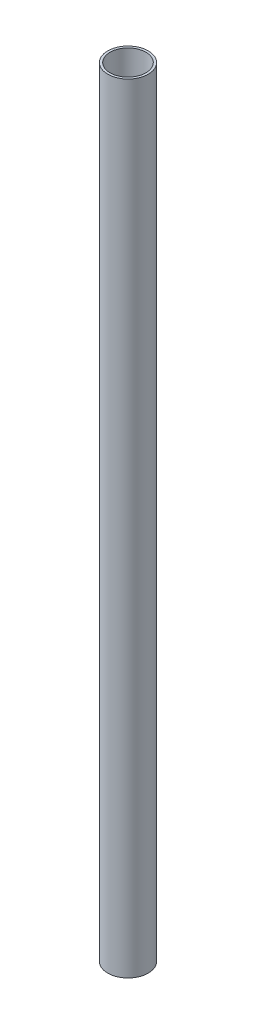
SolidWorks part; units mm, degrees
ref_plane "前视基准面" through (0, 0, 0) normal (0, 0, 1) x (1, 0, 0)
ref_plane "上视基准面" through (0, 0, 0) normal (0, 1, 0) x (1, 0, 0)
ref_plane "右视基准面" through (0, 0, 0) normal (1, 0, 0) x (0, 0, -1)
sketch "草图1" plane through (0, 0, 0) normal (0, 1, 0) x (1, 0, 0)
  circle A0 centre (0, 0) radius 13
  dimension "D1" = 26
extrude "凸台-拉伸1" add sketch "草图1" along normal blind 20
sketch "草图2" plane through (0, 20, 0) normal (0, 1, 0) x (1, 0, 0)
  circle A0 centre (0, 0) radius 13
  dimension "D1" = 26
extrude "凸台-拉伸2" add sketch "草图2" along normal blind 480
sketch "草图4" plane through (0, 0, 0) normal (0, -1, 0) x (1, 0, 0)
  circle A0 centre (0, 0) radius 11.5
  dimension "D1" = 23
extrude "切除-拉伸1" cut sketch "草图4" against normal through all
